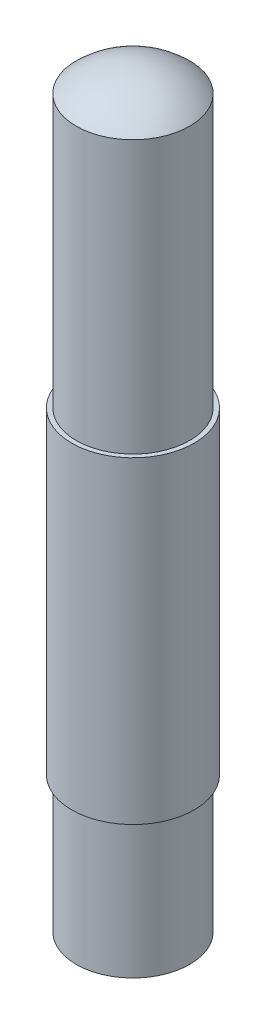
SolidWorks part; units mm, degrees
ref_plane "Front Plane" through (0, 0, 0) normal (0, 0, 1) x (1, 0, 0)
ref_plane "Top Plane" through (0, 0, 0) normal (0, 1, 0) x (1, 0, 0)
ref_plane "Right Plane" through (0, 0, 0) normal (1, 0, 0) x (0, 0, -1)
sketch "Sketch1" plane through (0, 0, 0) normal (0, 0, 1) x (1, 0, 0)
  line L0 (0, 0) -> (-12.5, 0)
  line L1 (-12.5, 0) -> (-12.5, 30)
  line L2 (-12.5, 30) -> (-13.5, 30)
  line L3 (-13.5, 30) -> (-13.5, 100)
  line L4 (-13.5, 100) -> (-12.5, 100)
  line L5 (-12.5, 100) -> (-12.5, 160)
  line L6 (-12.5, 160) -> (0, 160)
  line L7 (0, 160) -> (0, 0) construction
  line L8 (0, 0) -> (0, 160)
  dimension "D1" = 160
  dimension "D2" = 60
  dimension "D3" = 70
  dimension "D4" = 12.5
  dimension "D5" = 13.5
  dimension "D6" = 12.5
revolve "Revolve2" add sketch "Sketch1" angle 360 about L7
cosmetic thread "Cosmetic Thread1" parameters "D2"=23.38
cosmetic thread "Cosmetic Thread2" parameters "D2"=23.38
dome "Dome1" faces to dome 1 distance 5 reverse direction no elliptical dome no face at (0, 160, 12.5) parameters "D1"=5
